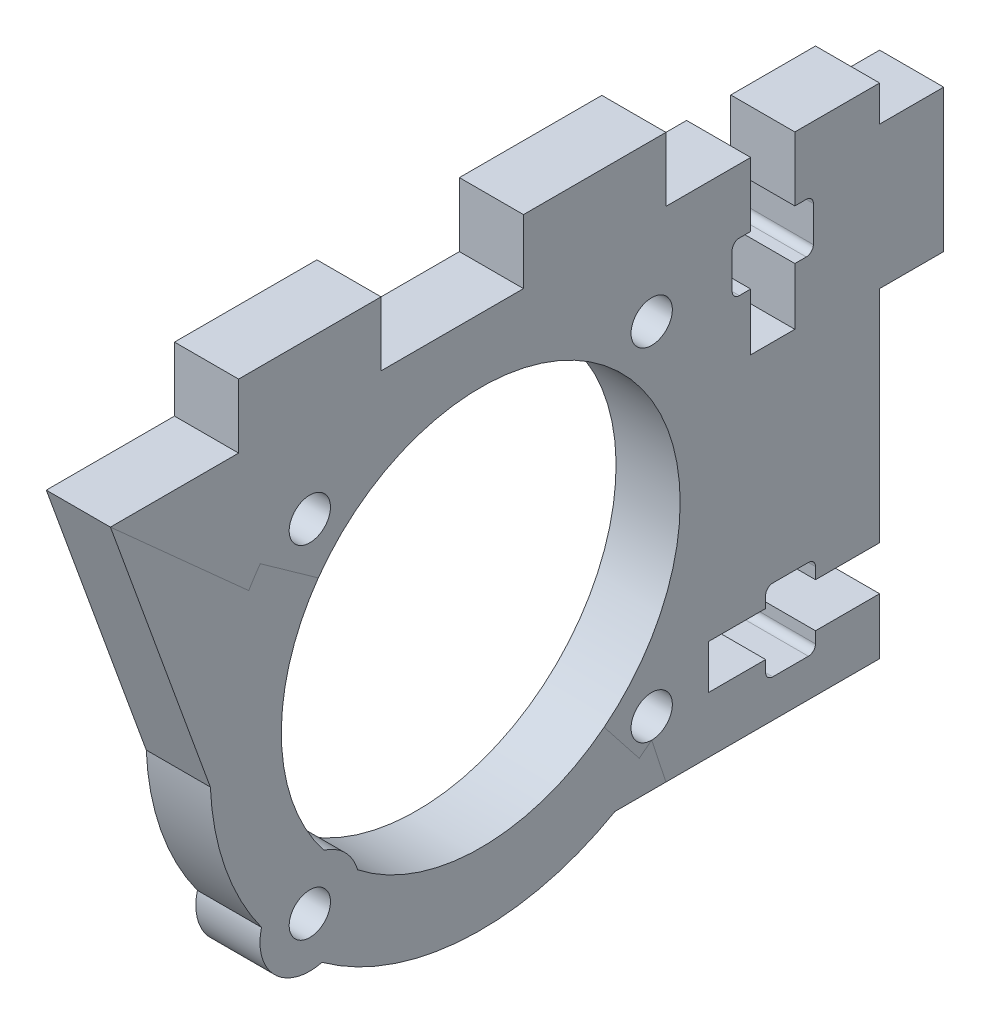
SolidWorks part; units mm, degrees
ref_plane "Front Plane" through (0, 0, 0) normal (0, 0, 1) x (1, 0, 0)
ref_plane "Top Plane" through (0, 0, 0) normal (0, 1, 0) x (1, 0, 0)
ref_plane "Right Plane" through (0, 0, 0) normal (1, 0, 0) x (0, 0, -1)
sketch "Sketch1" plane through (0, 0, 0) normal (1, 0, 0) x (0, 0, -1)
  line L0 (0, 0) -> (0, -35)
  line L1 (0, -35) -> (-54, 0)
  line L2 (-54, 0) -> (0, 0)
  dimension "D1" = 35
  dimension "D2" = 54
extrude "Boss-Extrude1" add sketch "Sketch1" along normal blind 4.5
sketch "Sketch2" plane through (4.5, 0, 0) normal (1, 0, 0) x (0, 0, -1)
  line L0 (0, -35) -> (0, 0) construction
  line L1 (-4.5, -2.5) -> (4.5, -2.5)
  line L2 (-4.5, -2.5) -> (-4.5, -12.5)
  line L3 (-4.5, -12.5) -> (4.5, -12.5)
  line L4 (4.5, -2.5) -> (4.5, -12.5)
  line L5 (-4.5, -2.5) -> (4.5, -12.5) construction
  line L6 (-4.5, -12.5) -> (4.5, -2.5) construction
  line L7 (0, 0) -> (-54, 0) construction
  point P0 (0, -7.5)
  dimension "D1" = 10
  dimension "D2" = 7.5
  dimension "D3" = 4.5
extrude "Boss-Extrude2" add sketch "Sketch2" against normal through all
sketch "Sketch3" plane through (4.5, 0, 0) normal (1, 0, 0) x (0, 0, -1)
  line L0 (0, -35) -> (-15, -35)
  line L1 (0, -25) -> (-54, 0)
  line L4 (0, -35) -> (0, -12.5) construction
  line L5 (0, -25) -> (0, -35)
  line L6 (-54, 0) -> (-15, -35)
  dimension "D1" = 15
  dimension "D2" = 10
extrude "Boss-Extrude3" add sketch "Sketch3" against normal through all
sketch "Sketch4" plane through (4.5, 0, 0) normal (1, 0, 0) x (0, 0, -1)
  line L0 (0, -29.5) -> (-12, -29.5) construction
  line L1 (0, -35) -> (0, -12.5) construction
  line L2 (0, -27.95) -> (-12, -27.95) construction
  line L3 (-12, -27.95) -> (-12, -31.05) construction
  line L4 (0, -31.05) -> (0, -27.95)
  line L5 (0, -27.95) -> (-4.5, -27.95)
  line L6 (-4.5, -27.95) -> (-4.5, -27.15)
  line L7 (-5, -26.65) -> (-7.5, -26.65)
  line L8 (-8, -27.15) -> (-8, -27.95)
  line L9 (-8, -27.95) -> (-12, -27.95)
  line L10 (-12, -27.95) -> (-12, -31.05)
  line L12 (0, -31.05) -> (-12, -31.05) construction
  line L13 (-8, -31.05) -> (-12, -31.05)
  line L14 (-8, -31.85) -> (-8, -31.05)
  line L15 (-5, -32.35) -> (-7.5, -32.35)
  line L16 (-4.5, -31.05) -> (-4.5, -31.85)
  line L17 (0, -31.05) -> (-4.5, -31.05)
  line L18 (4.5, -12.5) -> (4.5, -2.5) construction
  line L19 (0, -18.5) -> (-33.3857, -18.5) construction
  line L20 (-54, 0) -> (-15, -35) construction
  line L37 (0, -31.05) -> (-12, -31.05) construction
  arc A0 (-8, -31.85) -> (-7.5, -32.35) centre (-7.5, -31.85) ccw
  arc A1 (-5, -32.35) -> (-4.5, -31.85) centre (-5, -31.85) ccw
  arc A2 (-4.5, -27.15) -> (-5, -26.65) centre (-5, -27.15) ccw
  arc A3 (-7.5, -26.65) -> (-8, -27.15) centre (-7.5, -27.15) ccw
  point P10 (4.5, -7.5)
  point P20 (-8, -32.35)
  point P23 (-4.5, -32.35)
  point P26 (-4.5, -26.65)
  point P29 (-8, -26.65)
  dimension "D7" = 0.5
  dimension "D1" = 12
  dimension "D2" = 1.55
  dimension "D3" = 2.85
  dimension "D4" = 3.5
  dimension "D5" = 8
  dimension "D6" = 22
extrude "Cut-Extrude1" cut sketch "Sketch4" against normal through all
sketch "Sketch5" plane through (4.5, 0, 0) normal (1, 0, 0) x (0, 0, -1)
  line L0 (0, 0) -> (-54, 0) construction
  line L1 (-25, 4.5) -> (-15, 4.5)
  line L2 (-25, 4.5) -> (-25, 0)
  line L3 (0, 0) -> (-54, 0) construction
  line L4 (-15, 4.5) -> (-15, 0)
  line L5 (-25, 4.5) -> (-20, 0) construction
  line L6 (-20, 0) -> (-15, 4.5) construction
  line L7 (-30, 0) -> (-30, 4.5) construction
  line L8 (-40, 0) -> (-45, 4.5) construction
  line L9 (-35, 4.5) -> (-40, 0) construction
  line L10 (-45, 4.5) -> (-45, 0)
  line L12 (-35, 4.5) -> (-35, 0)
  line L13 (-35, 4.5) -> (-45, 4.5)
  line L14 (-20, 0) -> (-15, 4.5) construction
  line L15 (-15, 0) -> (-25, 0)
  line L16 (-35, 0) -> (-45, 0)
  point P0 (-20, 0)
  point P14 (-40, 0)
  dimension "D3" = 4.5
  dimension "D1" = 20
  dimension "D2" = 10
  dimension "D4" = 20
  dimension "D5" = 5
extrude "Boss-Extrude4" add sketch "Sketch5" against normal through all
sketch "Sketch8" [suppressed] plane through (4.5, 0, 0) normal (1, 0, 0) x (0, 0, -1)
  line L0 (-15, -30) -> (-27, -30) construction
  line L1 (-15, -35) -> (-27, -35)
  line L2 (-15, -25) -> (-27, -25)
  line L3 (-15, -35) -> (0, -35) construction
  line L4 (-15, -25) -> (-15, -35)
  arc A1 (-27, -25) -> (-27, -35) centre (-27, -30) ccw
  dimension "D5" = 5
  dimension "D1" = 0
  dimension "D2" = 12
  dimension "D3" = 0
  dimension "D4" = 10
extrude "Boss-Extrude5" [suppressed] add sketch "Sketch8" against normal up to surface (4.5 mm away) up to face at (0, -17.3125, 11.9375)
sketch "Sketch9" [suppressed] plane through (4.5, 0, 0) normal (1, 0, 0) x (0, 0, -1)
  line L0 (-27, -30) -> (-22, -30) construction
  line L1 (-27, -27) -> (-22, -27)
  line L2 (-27, -33) -> (-22, -33)
  arc A0 (-27, -27) -> (-27, -33) centre (-27, -30) ccw
  arc A1 (-22, -33) -> (-22, -27) centre (-22, -30) ccw
  point P3 (-24.5, -30)
  dimension "D1" = 3
  dimension "D2" = 5
extrude "Cut-Extrude3" [suppressed] cut sketch "Sketch9" against normal through all
sketch "Sketch10" plane through (0, 0, 0) normal (-1, 0, 0) x (0, 0, 1)
  line L0 (15, -35) -> (54, -12)
  line L1 (54, -12) -> (54, 0)
  line L3 (54, 0) -> (15, -35)
  dimension "D1" = 12
extrude "Boss-Extrude6" [suppressed] add sketch "Sketch10" against normal through all
sketch "Sketch6" plane through (4.5, 0, 0) normal (1, 0, 0) x (0, 0, -1)
  line L0 (-30, 0) -> (-30, -11) construction
  line L1 (-25, 0) -> (-35, 0) construction
  line L2 (-28.45, -11) -> (-31.55, -11) construction
  line L3 (-31.55, -11) -> (-31.55, 0) construction
  line L4 (-28.45, 0) -> (-31.55, 0)
  line L5 (-31.55, 0) -> (-31.55, -4.5)
  line L6 (-31.55, -4.5) -> (-32.35, -4.5)
  line L7 (-32.85, -5) -> (-32.85, -7.5)
  line L8 (-32.35, -8) -> (-31.55, -8)
  line L9 (-31.55, -8) -> (-31.55, -11)
  line L10 (-31.55, -11) -> (-28.45, -11)
  line L11 (-28.45, -11) -> (-28.45, 0) construction
  line L12 (-28.45, -8) -> (-28.45, -11)
  line L13 (-27.65, -8) -> (-28.45, -8)
  line L14 (-27.15, -5) -> (-27.15, -7.5)
  line L15 (-28.45, -4.5) -> (-27.65, -4.5)
  line L16 (-28.45, 0) -> (-28.45, -4.5)
  arc A0 (-32.85, -7.5) -> (-32.35, -8) centre (-32.35, -7.5) ccw
  arc A1 (-32.35, -4.5) -> (-32.85, -5) centre (-32.35, -5) ccw
  arc A2 (-27.65, -4.5) -> (-27.15, -5) centre (-27.65, -5) cw
  arc A3 (-27.15, -7.5) -> (-27.65, -8) centre (-27.65, -7.5) cw
  point P12 (-32.85, -8)
  point P15 (-32.85, -4.5)
  point P26 (-27.15, -4.5)
  point P27 (-27.15, -8)
  dimension "D2" = 1.55
  dimension "D4" = 3.5
  dimension "D6" = 0.5
  dimension "D1" = 11
  dimension "D3" = 8
  dimension "D5" = 2.85
extrude "Cut-Extrude2" [suppressed] cut sketch "Sketch6" against normal through all
sketch "Sketch11" plane through (0, 0, 0) normal (-1, 0, 0) x (0, 0, 1)
  line L0 (7.5, 0) -> (7.5, -12) construction
  line L1 (0, 0) -> (15, 0) construction
  line L2 (5.95, -12) -> (9.05, -12)
  line L3 (9.05, -12) -> (9.05, -8)
  line L4 (9.05, -8) -> (9.85, -8)
  line L5 (10.35, -7.5) -> (10.35, -5)
  line L6 (9.85, -4.5) -> (9.05, -4.5)
  line L7 (9.05, -4.5) -> (9.05, 0)
  line L8 (9.05, 0) -> (5.95, 0)
  line L9 (9.05, -8) -> (9.05, -4.5) construction
  line L10 (0, 0) -> (15, 0) construction
  line L11 (5.95, -8) -> (5.95, -4.5) construction
  line L12 (5.95, -4.5) -> (5.95, 0)
  line L13 (5.15, -4.5) -> (5.95, -4.5)
  line L14 (4.65, -7.5) -> (4.65, -5)
  line L15 (5.95, -8) -> (5.15, -8)
  line L16 (5.95, -12) -> (5.95, -8)
  arc A0 (10.35, -5) -> (9.85, -4.5) centre (9.85, -5) ccw
  arc A1 (5.15, -4.5) -> (4.65, -5) centre (5.15, -5) ccw
  arc A2 (9.85, -8) -> (10.35, -7.5) centre (9.85, -7.5) ccw
  arc A3 (4.65, -7.5) -> (5.15, -8) centre (5.15, -7.5) ccw
  point P11 (7.5, 0)
  point P22 (10.35, -4.5)
  point P25 (4.65, -4.5)
  point P28 (10.35, -8)
  point P31 (4.65, -8)
  dimension "D7" = 0.5
  dimension "D1" = 12
  dimension "D3" = 2.85
  dimension "D8" = 0.5
  dimension "D2" = 3.5
  dimension "D4" = 8
  dimension "D5" = 1.55
  dimension "D6" = 0
extrude "Cut-Extrude4" cut sketch "Sketch11" against normal through all
sketch "Sketch12" plane through (0, 0, 0) normal (-1, 0, 0) x (0, 0, 1)
  line L0 (28, -18.5) -> (16, -6.5) construction
  line L1 (28, -18.5) -> (28, -4.5) construction
  line L2 (28, -18.5) -> (40, -6.5) construction
  line L3 (28, -18.5) -> (14, -18.5) construction
  line L4 (28, -18.5) -> (16, -30.5) construction
  line L5 (28, -18.5) -> (16, -6.5) construction
  line L6 (0, -27.95) -> (0, -12.5) construction
  line L7 (25, 0) -> (35, 0) construction
  circle A0 centre (28, -18.5) radius 14
  circle A1 centre (16, -6.5) radius 1.45
  circle A2 centre (40, -6.5) radius 1.45
  circle A3 centre (16, -30.5) radius 1.45
  dimension "D1" = 28
  dimension "D2" = 2.9
  dimension "D3" = 12
  dimension "D4" = 45
  dimension "D5" = 28
  dimension "D6" = 18.5
extrude "FanCutout" cut sketch "Sketch12" against normal through all
sketch "Sketch13" plane through (0, 0, 0) normal (-1, 0, 0) x (0, 0, 1)
  line L0 (39.4071, -10.3834) -> (43.481, -7.4847)
  line L1 (19.3358, -29.4969) -> (16.2414, -33.4243)
  line L6 (28, -18.5) -> (54, 0) construction
  line L7 (28, -18.5) -> (15, -35) construction
  arc A0 (19.3358, -29.4969) -> (39.4071, -10.3834) centre (28, -18.5) ccw
  arc A1 (16.2414, -33.4243) -> (43.481, -7.4847) centre (28, -18.5) ccw
  arc A3 (40.4722, -12.1404) -> (20.333, -30.214) centre (28, -18.5) ccw construction
  dimension "D1" = 5
extrude "Boss-Extrude7" add sketch "Sketch13" against normal through all
sketch "Sketch14" plane through (0, 0, 0) normal (-1, 0, 0) x (0, 0, 1)
  line L0 (28, -4.5) -> (28, -32.5) construction
  line L1 (28, -18.5) -> (40, -30.5) construction
  circle A0 centre (28, -18.5) radius 14 construction
  circle A1 centre (40, -30.5) radius 3.5
  dimension "D2" = 7
  dimension "D1" = 45
  dimension "D3" = 12
extrude "Boss-Extrude8" add sketch "Sketch14" against normal through all
sketch "Sketch15" plane through (0, 0, 0) normal (-1, 0, 0) x (0, 0, 1)
  line L0 (42.4749, -32.9749) -> (28, -18.5) construction
  arc A0 (39.1388, -33.8924) -> (43.3924, -29.6388) centre (40, -30.5) ccw construction
  circle A1 centre (40, -30.5) radius 1.45
  dimension "D1" = 2.9
extrude "Cut-Extrude6" cut sketch "Sketch15" against normal through all
sketch "Sketch16" [suppressed] plane through (4.5, 0, 0) normal (1, 0, 0) x (0, 0, -1)
  line L0 (0, -34.5) -> (-39, -34.5) construction
  line L1 (0, -27.95) -> (0, -12.5) construction
  line L2 (-15, -34.5) -> (-39, -34.5) construction
  line L3 (-15, -38.5) -> (-39, -38.5)
  line L4 (-15, -30.5) -> (-39, -30.5)
  arc A0 (-15, -38.5) -> (-15, -30.5) centre (-15, -34.5) ccw
  arc A1 (-39, -30.5) -> (-39, -38.5) centre (-39, -34.5) ccw
  point P5 (-27, -34.5)
  point P12 (0, -20.225)
  dimension "D1" = 4
  dimension "D2" = 34.5
  dimension "D3" = 39
  dimension "D4" = 15
extrude "Boss-Extrude9" [suppressed] add sketch "Sketch16" against normal through all
sketch "Sketch17" [suppressed] plane through (4.5, 0, 0) normal (1, 0, 0) x (0, 0, -1)
  line L0 (-43, -34.5) -> (0, -34.5) construction
  line L1 (0, -27.75) -> (0, -12.5) construction
  line L2 (-26.5, -34.5) -> (-26.5, -20.0064) construction
  arc A0 (-42.1823, -32.0766) -> (-39, -38.5) centre (-39, -34.5) ccw construction
  circle A1 centre (-39, -34.5) radius 1.55
  circle A2 centre (-14, -34.5) radius 1.55
  dimension "D1" = 2.9
  dimension "D2" = 12.5
extrude "Cut-Extrude7" [suppressed] cut sketch "Sketch17" against normal through all
sketch "Sketch18" [suppressed] plane through (4.5, 0, 0) normal (1, 0, 0) x (0, 0, -1)
  line L0 (-15, -38.5) -> (0, -35)
  line L1 (0, -35) -> (-11.0314, -35)
  line L2 (-11.0314, -35) -> (-15, -38.5)
extrude "Boss-Extrude10" [suppressed] add sketch "Sketch18" against normal through all
sketch "Sketch20" [suppressed] plane through (4.5, 0, 0) normal (1, 0, 0) x (0, 0, -1)
  line L0 (0, -35) -> (0, -31.05) construction
  line L1 (-9, -38) -> (-37.9081, -38)
  line L2 (-40.7232, -36.0371) -> (-54, 0)
  line L3 (-54, 0) -> (-15, -35)
  line L4 (-15, -35) -> (-6, -35)
  line L5 (-9, -38) -> (-6, -35)
  line L6 (-40.7232, -36.0371) -> (-40, -38) construction
  line L7 (-40, -38) -> (-37.9081, -38) construction
  arc A1 (-37.9081, -38) -> (-40.7232, -36.0371) centre (-37.9081, -35) cw
  point P0 (0, -33.025)
  point P14 (-40, -38)
  dimension "D3" = 6
  dimension "D4" = 3
  dimension "D1" = 40
  dimension "D2" = 3
  dimension "D5" = 135
extrude "Boss-Extrude11" [suppressed] add sketch "Sketch20" against normal through all
sketch "Sketch21" [suppressed] plane through (4.5, 0, 0) normal (1, 0, 0) x (0, 0, -1)
  line L0 (0, -34.5) -> (-41.2895, -34.5) construction
  line L1 (0, -35) -> (0, -31.05) construction
  line L2 (-54, 0) -> (-40.7232, -36.0371) construction
  line L3 (0, -27.95) -> (0, -12.5) construction
  circle A0 centre (-36, -34.5) radius 1.45
  circle A1 centre (-11, -34.5) radius 1.45
  dimension "D2" = 2.9
  dimension "D3" = 2.9
  dimension "D1" = 25
  dimension "D4" = 34.5
  dimension "D5" = 11
extrude "Cut-Extrude8" [suppressed] cut sketch "Sketch21" against normal through all
sketch "Sketch22" [suppressed] plane through (4.5, 0, 0) normal (1, 0, 0) x (0, 0, -1)
  line L0 (0, -27.95) -> (0, -12.5) construction
  line L1 (-25, 0) -> (-35, 0) construction
  circle A0 centre (-28, -18) radius 13.25
  dimension "D2" = 18
  dimension "D3" = 26.5
  dimension "D1" = 28
extrude "Cut-Extrude9" [suppressed] cut sketch "Sketch22" against normal through all
sketch "Sketch24" plane through (0, 0, 0) normal (-1, 0, 0) x (0, 0, 1)
  line L0 (15, -35) -> (20, -35)
  line L1 (20, -35) -> (16, -31.95)
  line L2 (16, -31.95) -> (15, -35)
  circle A0 centre (16, -30.5) radius 1.45 construction
  dimension "D1" = 5
extrude "Boss-Extrude13" add sketch "Sketch24" against normal through all
sketch "Sketch25" plane through (0, 0, 0) normal (-1, 0, 0) x (0, 0, 1)
  line L0 (54, 0) -> (46.9826, -19.3121)
  line L1 (46.9826, -19.3121) -> (44.2874, -8.7164)
  line L2 (44.2874, -8.7164) -> (54, 0)
  arc A0 (43.3924, -29.6388) -> (44.2874, -8.7164) centre (28, -18.5) ccw construction
extrude "Boss-Extrude15" add sketch "Sketch25" against normal through all
equation "\"X-ROD-SPACING\"=45"
equation "\"Y-ROD-SPACING\"=75"
equation "\"Z-ROD-SPACING\"=17.5"
equation "\"Y-BED-OFFSET\"=2"
equation "\"Y-BED-ROD-INSET\"=3.5"
equation "\"Y-BED-SCREW-SPACING\"=209"
equation "\"Y-BED-SCREW-CUTOUT-SLOT-HEIGHT\"=2.5"
equation "\"T-SLOT-NUT-FILLET-RADIUS\"=0.5"
equation "\"T-SLOT-SCREW-SHAFT-RADIUS\"=1.55"
equation "\"T-SLOT-SCREW-SHAFT-CUTOUT-LENGTH\"=11"
equation "\"T-SLOT-NUT-DEPTH\"=3.5"
equation "\"T-SLOT-NUT-WIDTH\"=2.85"
equation "\"T-SLOT-NUT-END-DISTANCE\"=8"
equation "\"ACRYLIC-THICKNESS\"=10"
equation "\"ACRYLIC-THICKNESS2\"=4.5"
equation "\"ACRYLIC-TAB-CUTOUT-SIZE\"=\"ACRYLIC-THICKNESS\"+\"ACRYLIC-TAB-TOLERANCE\"*2"
equation "\"ACRYLIC-TAB-WIDTH\"=\"ACRYLIC-THICKNESS\""
equation "\"ACRYLIC-M3-HOLE\"=2.9"
equation "\"SMOOTHROD-CAP-SCREW-DISTANCE\"=20"
equation "\"FRAME-WIDTH-INNER\"=370"
equation "\"NEMA17-HOLE-SPACING\"=31"
equation "\"NEMA17-CENTRAL-CUTOUT\"=22.5"
equation "\"Z-BRACKET-REACH\"=57"
equation "\"Z-ROD-INSET\"=13.5"
equation "\"TOP-BRACKET-SPACING\"=40"
equation "\"SMOOTHROD-X-LENGTH\"=350"
equation "\"SMOOTHROD-Y-LENGTH\"=350"
equation "\"SMOOTHROD-Z-LENGTH\"=350"
equation "\"SMOOTHROD-TIGHTENING-HEADROOM\"=.25"
equation "\"LEADSCREW-Z-LENGTH\"=300"
equation "\"SCREW-LENGTH-FRAME\"=\"ACRYLIC-THICKNESS\" + 10"
equation "\"SCREW-LENGTH-MOTOR\"=\"ACRYLIC-THICKNESS\" + 5"
equation "\"SCREW-LENGTH-EXTRUDER\"=28"
equation "\"SCREW-HEAD-RADIUS\"=6"
equation "\"PRINTED-X-SMOOTHROD-DIAMETER\"=8.8"
equation "\"PRINTED-X-SMOOTHROD-CUTOUT\"=10"
equation "\"PRINTED-X-BASE-HEIGHT\"=10"
equation "\"PRINTED-LM8UU-CUTOUT-SIZE\"=15.5"
equation "\"PRINTED-LM8UU-CUTOUT-LENGTH\"=24.5"
equation "\"PRINTED-X-IDLER-HEIGHT\"=16"
equation "\"PSU-MOUNTING-WIDTH\"=95"
equation "\"PSU-MOUNTING-HEIGHT\"=177"
equation "\"Y-BELT-TO-ROD-DISTANCE\"=20"
equation "\"SPOOL-HOLDER-ROD-SPACING\"=150"
equation "\"ACRYLIC-X-CARRIAGE-WIDTH\"=55"
equation "\"ACRYLIC-X-CARRIAGE-HEIGHT\"=75"
equation "\"ACRYLIC-X-CARRIAGE-SCREW-SPACING-X\"=15"
equation "\"ACRYLIC-X-CARRIAGE-SCREW-SPACING-Y\"=33"
equation "\"ACRYLIC-X-CARRIAGE-CENTER-TAB-SPACING\"=14"
equation "\"ACRYLIC-X-CARRIAGE-EXTRUDER-SHELF-DEPTH\"=\"ACRYLIC-X-CARRIAGE-EXTRUDER-OFFSET\" + 28"
equation "\"D2@Sketch1\"=\"ACRYLIC-X-CARRIAGE-EXTRUDER-SHELF-DEPTH\""
equation "\"D1@Boss-Extrude1\"=\"ACRYLIC-THICKNESS2\""
equation "\"D1@Sketch2\"=\"ACRYLIC-TAB-WIDTH\""
equation "\"D3@Sketch2\"=\"ACRYLIC-THICKNESS2\""
equation "\"ACRYLIC-X-CARRIAGE-LM8UU-CUTOUT-WIDTH\"=24.25"
equation "\"ACRYLIC-X-CARRIAGE-EXTRUDER-BRACE-SPACING\"=23"
equation "\"ACRYLIC-X-CARRIAGE-EXTRUDER-BRACE-HEIGHT\"=35"
equation "\"D1@Sketch1\"=\"ACRYLIC-X-CARRIAGE-EXTRUDER-BRACE-HEIGHT\""
equation "\"D1@Sketch4\"=\"T-SLOT-SCREW-SHAFT-CUTOUT-LENGTH\"+1"
equation "\"D2@Sketch4\"=\"T-SLOT-SCREW-SHAFT-RADIUS\""
equation "\"D3@Sketch4\"=\"T-SLOT-NUT-WIDTH\""
equation "\"D4@Sketch4\"=\"T-SLOT-NUT-DEPTH\""
equation "\"D5@Sketch4\"=\"T-SLOT-NUT-END-DISTANCE\""
equation "\"D7@Sketch4\"=\"T-SLOT-NUT-FILLET-RADIUS\""
equation "\"ACRYLIC-X-CARRIAGE-EXTRUDER-BRACE-SCREW-SPACING\"=22"
equation "\"D6@Sketch4\"=\"ACRYLIC-X-CARRIAGE-EXTRUDER-BRACE-SCREW-SPACING\""
equation "\"ACRYLIC-X-CARRIAGE-EXTRUDER-BRACE-TAB-OFFSET\"=20"
equation "\"D1@Sketch5\"=\"ACRYLIC-X-CARRIAGE-EXTRUDER-BRACE-TAB-OFFSET\""
equation "\"D2@Sketch5\"=\"ACRYLIC-TAB-WIDTH\""
equation "\"D3@Sketch5\"=\"ACRYLIC-THICKNESS2\""
equation "\"ACRYLIC-X-CARRIAGE-EXTRUDER-OFFSET\"=26"
equation "\"ACRYLIC-X-CARRIAGE-EXTRUDER-ANGLE\"=90"
equation "\"D1@Sketch6\"=\"T-SLOT-SCREW-SHAFT-CUTOUT-LENGTH\""
equation "\"D2@Sketch6\"=\"T-SLOT-SCREW-SHAFT-RADIUS\""
equation "\"D3@Sketch6\"=\"T-SLOT-NUT-END-DISTANCE\""
equation "\"D4@Sketch6\"=\"T-SLOT-NUT-DEPTH\""
equation "\"D5@Sketch6\"=\"T-SLOT-NUT-WIDTH\""
equation "\"D6@Sketch6\"=\"T-SLOT-NUT-FILLET-RADIUS\""
equation "\"D1@Sketch11\"=\"T-SLOT-SCREW-SHAFT-CUTOUT-LENGTH\"+1"
equation "\"D2@Sketch11\"=\"T-SLOT-NUT-DEPTH\""
equation "\"D3@Sketch11\"=\"T-SLOT-NUT-WIDTH\""
equation "\"D4@Sketch11\"=\"T-SLOT-NUT-END-DISTANCE\""
equation "\"D5@Sketch11\"=\"T-SLOT-SCREW-SHAFT-RADIUS\""
equation "\"D7@Sketch11\"=\"T-SLOT-NUT-FILLET-RADIUS\""
equation "\"D8@Sketch11\"=\"T-SLOT-NUT-FILLET-RADIUS\""
equation "\"D2@Sketch12\"=\"ACRYLIC-M3-HOLE\""
equation "\"D1@Sketch15\"=\"ACRYLIC-M3-HOLE\""
equation "\"D1@Sketch17\"=\"ACRYLIC-M3-HOLE\""
equation "\"D2@Sketch21\"=\"ACRYLIC-M3-HOLE\""
equation "\"D3@Sketch21\"=\"ACRYLIC-M3-HOLE\""
